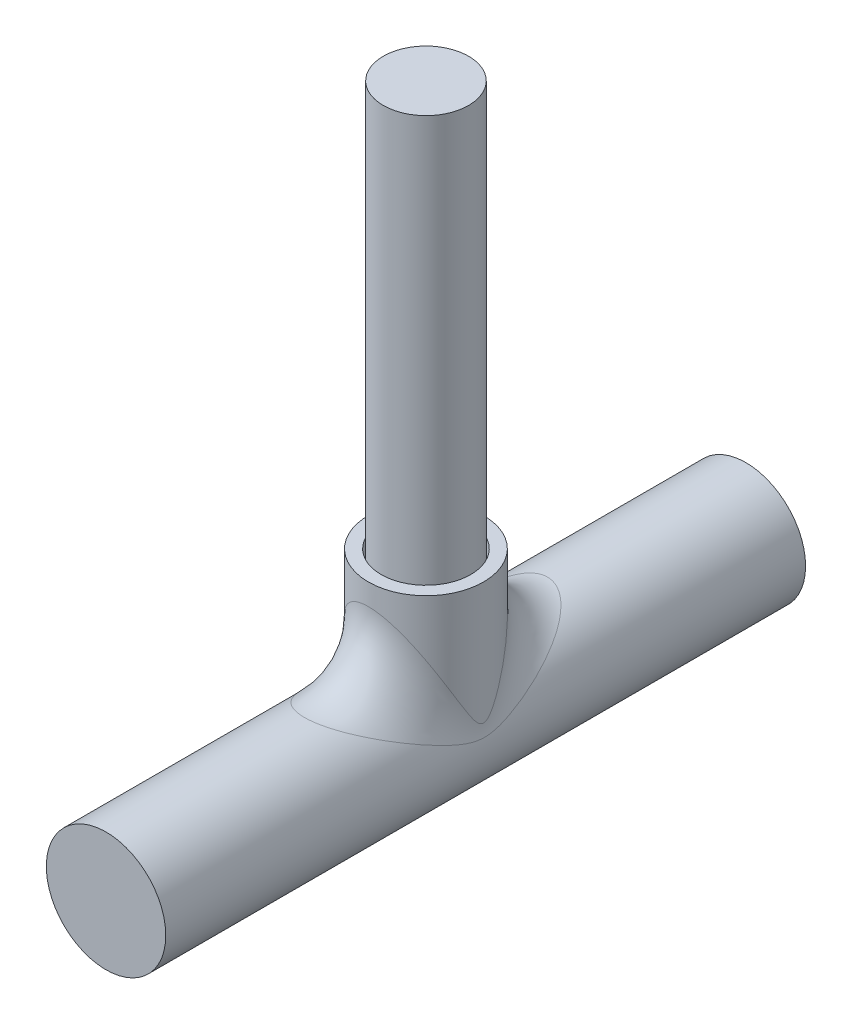
SolidWorks part; units mm, degrees
ref_plane "Front Plane" through (0, 0, 0) normal (0, 0, 1) x (1, 0, 0)
ref_plane "Top Plane" through (0, 0, 0) normal (0, 1, 0) x (1, 0, 0)
ref_plane "Right Plane" through (0, 0, 0) normal (1, 0, 0) x (0, 0, -1)
sketch "Sketch1" plane through (0, 0, 0) normal (0, 0, 1) x (1, 0, 0)
  line L0 (0, 0) -> (0, 14) construction
  circle A0 centre (0, 0) radius 14
  dimension "D1" = 28
extrude "Boss-Extrude1" add sketch "Sketch1" along normal mid plane 150
sketch "Sketch4" plane through (0, 0, -75) normal (0, 0, -1) x (-1, 0, 0)
  line L0 (0, 0) -> (0, 14) construction
  circle A0 centre (0, 0) radius 14 construction
ref_plane "Plane1" through (0, 14, 0) normal (0, 1, 0) x (1, 0, 0)
sketch "Sketch2" plane through (0, 14, 0) normal (0, 1, 0) x (1, 0, 0)
  circle A2 centre (0, 0) radius 13.5
  dimension "D1" = 27
extrude "Boss-Extrude3" add sketch "Sketch2" along normal blind 20 and the other way up to body separate body
fillet "Fillet1" radius 15 1 edges at (1.1285, 13.9544, 13.4528)
sketch "Sketch5" plane through (0, 34, 0) normal (0, 1, 0) x (1, 0, 0)
  circle A0 centre (0, 0) radius 10.5
  dimension "D1" = 21
extrude "Cut-Extrude1" cut sketch "Sketch5" against normal blind 35
sketch "Sketch6" plane through (0, -1, 0) normal (0, 1, 0) x (1, 0, 0)
  circle A0 centre (0, 0) radius 10
  dimension "D1" = 20
extrude "TIL ASSEMBLY - SLETT" add sketch "Sketch6" along normal blind 130
